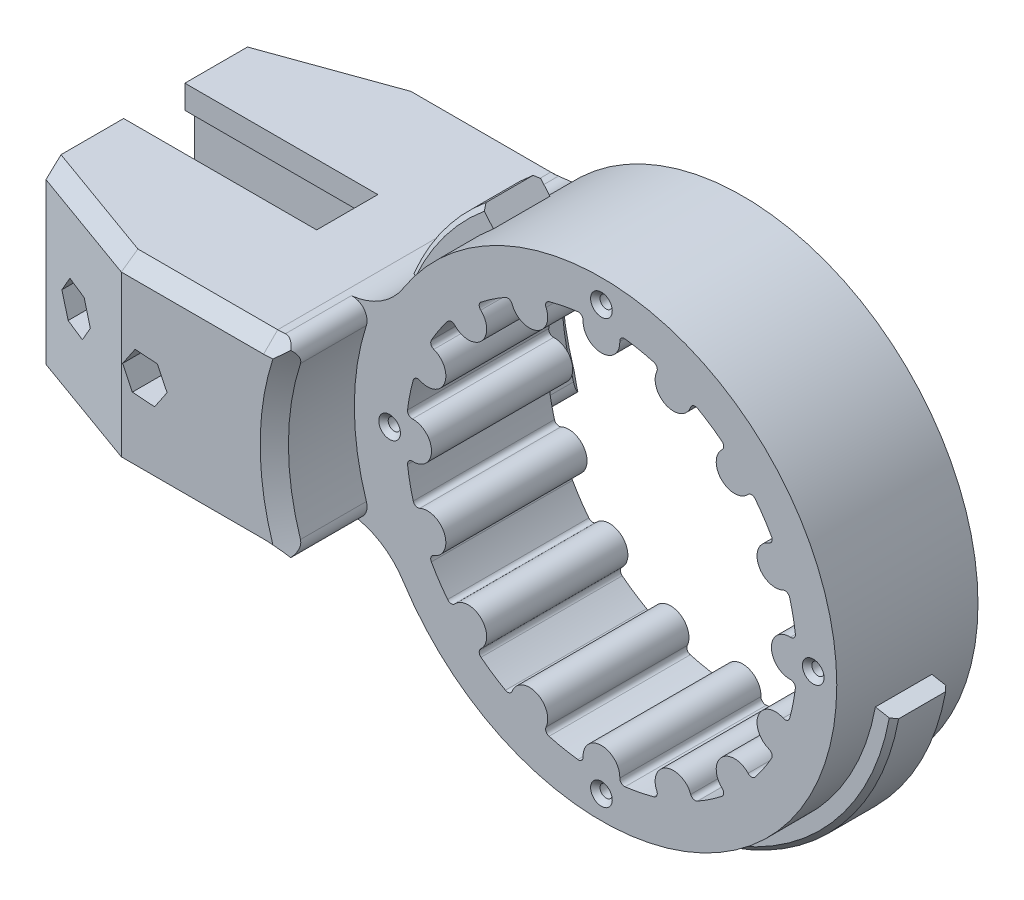
SolidWorks part; units mm, degrees
ref_plane "Front Plane" through (0, 0, 0) normal (0, 0, 1) x (1, 0, 0)
ref_plane "Top Plane" through (0, 0, 0) normal (0, 1, 0) x (1, 0, 0)
ref_plane "Right Plane" through (0, 0, 0) normal (1, 0, 0) x (0, 0, -1)
sketch "Sketch1" plane through (0, 0, 0) normal (0, 0, 1) x (1, 0, 0)
  circle A0 centre (0, 0) radius 50
  dimension "D1" = 100
extrude "Boss-Extrude1" add sketch "Sketch1" along normal blind 30
sketch "Sketch4" plane through (0, 0, 0) normal (0, 0, -1) x (-1, 0, 0)
  line L0 (50, 0) -> (110, 0) construction
  line L1 (45.8258, -20) -> (110, -20)
  line L2 (45.8258, 20) -> (110, 20)
  line L3 (110, 20) -> (110, -20)
  line L4 (0, 20) -> (110, 20) construction
  line L5 (0, 0) -> (110, 0) construction
  line L6 (0, -20) -> (110, -20) construction
  circle A0 centre (0, 0) radius 50 construction
  arc A1 (45.8258, -20) -> (45.8258, 20) centre (0, 0) ccw
  dimension "D3" = 110
  dimension "D1" = 20
  dimension "D2" = 20
extrude "Boss-Extrude2" add sketch "Sketch4" against normal up to surface (30 mm away) up to face at (50, 0, 30)
sketch "Sketch5" plane through (0, 0, 0) normal (0, 0, -1) x (-1, 0, 0)
  line L2 (110, -20) -> (110, 20)
  line L3 (110, 20) -> (48.5412, 20)
  line L5 (48.5412, -20) -> (110, -20)
  line L6 (0, 0) -> (139.0391, 0) construction
  arc A0 (48.5412, -20) -> (48.5412, 20) centre (0, 0) ccw
  dimension "D1" = 105
  dimension "D2" = 40
  dimension "D3" = 110
extrude "Boss-Extrude3" add sketch "Sketch5" along normal blind 17
sketch "Sketch6" plane through (0, 0, 30) normal (0, 0, 1) x (1, 0, 0)
  line L0 (-110, 0) -> (0, 0) construction
  line L6 (-110, -20) -> (-48.5412, -20)
  line L7 (-110, 20) -> (-110, -20)
  line L8 (-48.5412, 20) -> (-110, 20)
  arc A2 (-48.5412, 20) -> (-48.5412, -20) centre (0, 0) ccw
  dimension "D1" = 52.5
  dimension "D2" = 40
  dimension "D3" = 110
extrude "Boss-Extrude4" add sketch "Sketch6" along normal blind 17
sketch "Sketch7" plane through (0, 20, 0) normal (0, 1, 0) x (1, 0, 0)
  line L0 (50, -15) -> (-110, -15) construction
  line L1 (50, -30) -> (50, 0) construction
  line L2 (-110, -47) -> (-110, 17) construction
  line L4 (-151, -8.5) -> (-69, -8.5)
  line L5 (-151, -8.5) -> (-151, -21.5)
  line L6 (-151, -21.5) -> (-69, -21.5)
  line L7 (-69, -8.5) -> (-69, -21.5)
  line L8 (-151, -8.5) -> (-69, -21.5) construction
  line L9 (-151, -21.5) -> (-69, -8.5) construction
  dimension "D1" = 13
  dimension "D2" = 41
extrude "Cut-Extrude3" cut sketch "Sketch7" against normal through all
sketch "Sketch8" plane through (0, 20, 0) normal (0, 1, 0) x (1, 0, 0)
  line L0 (-110, 8) -> (-85, 17)
  line L1 (-110, -8.5) -> (-110, 17) construction
  line L2 (-110, 17) -> (-48.5412, 17) construction
  line L3 (-69, -15) -> (-102.4865, -15) construction
  line L4 (-69, -21.5) -> (-69, -8.5) construction
  line L5 (-110, -38) -> (-85, -47)
  line L6 (-110, -47) -> (-110, -21.5) construction
  line L7 (-48.5412, -47) -> (-110, -47) construction
  line L8 (-110, 17) -> (-85, 17)
  line L9 (-110, 8) -> (-110, 17)
  line L10 (-110, -47) -> (-110, -38)
  line L11 (-85, -47) -> (-110, -47)
  dimension "D1" = 9
  dimension "D2" = 25
extrude "Cut-Extrude4" cut sketch "Sketch8" against normal through all
fillet "Fillet3" radius 15 2 edges at (-45.8258, 20, 15) (-45.8258, -20, 15)
sketch "Sketch10" plane through (-110, 0, 0) normal (-1, 0, 0) x (0, 0, 1)
  line L0 (15, 20) -> (15, -20) construction
  line L1 (47, 20) -> (-17, 20) construction
  line L2 (-17, -20) -> (47, -20) construction
  line L3 (21.5, -20) -> (21.5, 20) construction
  line L4 (6.5, 15) -> (23.5, 15)
  line L5 (6.5, 15) -> (6.5, -15)
  line L6 (6.5, -15) -> (23.5, -15)
  line L7 (23.5, 15) -> (23.5, -15)
  line L8 (6.5, 15) -> (23.5, -15) construction
  line L9 (6.5, -15) -> (23.5, 15) construction
  point P6 (15, 0)
  dimension "D1" = 30
  dimension "D2" = 2
extrude "Cut-Extrude5" cut sketch "Sketch10" against normal blind 41
sketch "Sketch11" plane through (0, 0, -17) normal (0, 0, -1) x (-1, 0, 0)
  line L0 (110, 0) -> (45.4033, 0) construction
  line L1 (110, -20) -> (110, 20) construction
  circle A0 centre (100, 0) radius 2.75
  circle A1 centre (80, 0) radius 2.75
  dimension "D3" = 5.5
  dimension "D1" = 10
  dimension "D2" = 20
extrude "Cut-Extrude6" cut sketch "Sketch11" against normal through all
sketch "Sketch12" plane through (0, 0, -17) normal (0, 0, -1) x (-1, 0, 0)
  circle A0 centre (80, 0) radius 4.6
  circle A1 centre (100, 0) radius 4.6
  dimension "D1" = 9.2
extrude "Cut-Extrude7" cut sketch "Sketch12" against normal blind 12
sketch "Sketch13" plane through (0, 0, 47) normal (0, 0, 1) x (1, 0, 0)
  line L1 (-104.7224, 0.3346) -> (-102.651, -3.9225)
  line L2 (-102.651, -3.9225) -> (-97.9285, -4.257)
  line L3 (-97.9285, -4.257) -> (-95.2776, -0.3346)
  line L4 (-95.2776, -0.3346) -> (-97.349, 3.9225)
  line L5 (-97.349, 3.9225) -> (-102.0715, 4.257)
  line L6 (-102.0715, 4.257) -> (-104.7224, 0.3346)
  line L7 (-84.7224, 0.3346) -> (-82.651, -3.9225)
  line L8 (-82.651, -3.9225) -> (-77.9285, -4.257)
  line L9 (-77.9285, -4.257) -> (-75.2776, -0.3346)
  line L10 (-75.2776, -0.3346) -> (-77.349, 3.9225)
  line L11 (-77.349, 3.9225) -> (-82.0715, 4.257)
  line L12 (-82.0715, 4.257) -> (-84.7224, 0.3346)
  circle A0 centre (-100, 0) radius 4.1 construction
  circle A1 centre (-80, 0) radius 4.1 construction
  dimension "D1" = 8.2
extrude "Cut-Extrude8" cut sketch "Sketch13" against normal blind 12
sketch3d "3DSketch1"
  line L0 (-54.7723, 20, 47) -> (-85, 20, 47) construction
  line L1 (-85, -20, 47) -> (-85, 20, 47) construction
  point P0 (-54.8705, 20, 47)
  point P1 (-85, 11.3679, 47)
  point P4 (-110, 20, 38)
chamfer "Chamfer1" distance 3 angle 45 7 edges at (-97.5, 20, 42.5) (-69.8861, 20, 47) (-52.5, 0, 47) (-97.5, -20, 42.5) (-69.8861, -20, 47) (-51.1795, -20.4366, 47) (-51.1795, 20.4366, 47)
chamfer "Chamfer2" distance 3 angle 45 7 edges at (-97.5, -20, -12.5) (-69.8861, -20, -17) (-52.5, 0, -17) (-69.8861, 20, -17) (-97.5, 20, -12.5) (-51.1795, 20.4366, -17) (-51.1795, -20.4366, -17)
ref_plane "Plane2" through (0, 0, 15) normal (0, 0, 1) x (1, 0, 0)
fillet "Fillet5" radius 3 4 edges at (-47.7959, -21.7211, -7) (-47.7959, -21.7211, 37) (-47.7959, 21.7211, -7) (-47.7959, 21.7211, 37)
sketch "Sketch17" plane through (0, 0, 30) normal (0, 0, 1) x (1, 0, 0)
  circle A0 centre (0, 0) radius 45 construction
  circle A1 centre (-45, 0) radius 1.3
  circle A2 centre (0, 45) radius 1.3
  circle A3 centre (45, 0) radius 1.3
  circle A4 centre (0, -45) radius 1.3
  point P14 (0, 0)
  point P15 (0, 0)
  dimension "D1" = 90
  dimension "D2" = 2.6
  dimension "D3" = 4
extrude "Cut-Extrude10" cut sketch "Sketch17" against normal blind 93
chamfer "Chamfer3" distance 1 angle 45 4 edges at (-43.7, 0, 30) (1.3, 45, 30) (46.3, 0, 30) (1.3, -45, 30)
sketch "Sketch25" plane through (0, 0, 15) normal (0, 0, 1) x (1, 0, 0)
  circle A0 centre (0, 0) radius 54
  circle A1 centre (0, 0) radius 50
  arc A2 (-42.1325, -26.9231) -> (-42.1325, 26.9231) centre (0, 0) ccw construction
  dimension "D1" = 4
extrude "Boss-Extrude8" add sketch "Sketch25" along normal mid plane 12
sketch "Sketch26" plane through (0, 0, 21) normal (0, 0, 1) x (1, 0, 0)
  line L0 (53.1342, -9.6311) -> (49.1983, -8.9177)
  line L2 (-34.5124, 41.5319) -> (-31.9559, 38.4554)
  arc A0 (-49.8155, -20.8426) -> (-49.8155, 20.8426) centre (0, 0) ccw construction
  arc A1 (-42.1325, -26.9231) -> (-42.1325, 26.9231) centre (0, 0) ccw construction
  arc A2 (53.1342, -9.6311) -> (-34.5124, 41.5319) centre (0, 0) ccw
  arc A3 (49.1983, -8.9177) -> (-31.9559, 38.4554) centre (0, 0) ccw
  dimension "D1" = 140
extrude "Cut-Extrude12" cut sketch "Sketch26" against normal blind 15
chamfer "Chamfer4" distance 1 angle 45 4 edges at (5.8462, -53.6826, 21) (5.8462, -53.6826, 9) (-43.4144, 32.1122, 9) (-43.4144, 32.1122, 21)
sketch "Sketch27" plane through (0, 0, 30) normal (0, 0, 1) x (1, 0, 0)
  circle A0 centre (0, 0) radius 40 construction
  arc A1 (-41.338, -3.6633) -> (-41.338, 3.6633) centre (-40, 0) ccw
  arc A2 (-39.5932, 12.4349) -> (-36.7894, 19.2038) centre (-36.9552, 15.3073) ccw
  arc A3 (-31.8207, 26.64) -> (-26.64, 31.8207) centre (-28.2843, 28.2843) ccw
  arc A4 (-19.2038, 36.7894) -> (-12.4349, 39.5932) centre (-15.3073, 36.9552) ccw
  arc A5 (-3.6633, 41.338) -> (3.6633, 41.338) centre (0, 40) ccw
  arc A6 (12.4349, 39.5932) -> (19.2038, 36.7894) centre (15.3073, 36.9552) ccw
  arc A7 (26.64, 31.8207) -> (31.8207, 26.64) centre (28.2843, 28.2843) ccw
  arc A8 (36.7894, 19.2038) -> (39.5932, 12.4349) centre (36.9552, 15.3073) ccw
  arc A9 (41.338, 3.6633) -> (41.338, -3.6633) centre (40, 0) ccw
  arc A10 (39.5932, -12.4349) -> (36.7894, -19.2038) centre (36.9552, -15.3073) ccw
  arc A11 (31.8207, -26.64) -> (26.64, -31.8207) centre (28.2843, -28.2843) ccw
  arc A12 (19.2038, -36.7894) -> (12.4349, -39.5932) centre (15.3073, -36.9552) ccw
  arc A13 (3.6633, -41.338) -> (-3.6633, -41.338) centre (0, -40) ccw
  arc A14 (-12.4349, -39.5932) -> (-19.2038, -36.7894) centre (-15.3073, -36.9552) ccw
  arc A15 (-26.64, -31.8207) -> (-31.8207, -26.64) centre (-28.2843, -28.2843) ccw
  arc A16 (-36.7894, -19.2038) -> (-39.5932, -12.4349) centre (-36.9552, -15.3073) ccw
  arc A17 (-12.4349, -39.5932) -> (-3.6633, -41.338) centre (0, 0) ccw
  arc A18 (3.6633, -41.338) -> (12.4349, -39.5932) centre (0, 0) ccw
  arc A19 (19.2038, -36.7894) -> (26.64, -31.8207) centre (0, 0) ccw
  arc A20 (31.8207, -26.64) -> (36.7894, -19.2038) centre (0, 0) ccw
  arc A21 (39.5932, -12.4349) -> (41.338, -3.6633) centre (0, 0) ccw
  arc A22 (41.338, 3.6633) -> (39.5932, 12.4349) centre (0, 0) ccw
  arc A23 (36.7894, 19.2038) -> (31.8207, 26.64) centre (0, 0) ccw
  arc A24 (26.64, 31.8207) -> (19.2038, 36.7894) centre (0, 0) ccw
  arc A25 (12.4349, 39.5932) -> (3.6633, 41.338) centre (0, 0) ccw
  arc A26 (-3.6633, 41.338) -> (-12.4349, 39.5932) centre (0, 0) ccw
  arc A27 (-19.2038, 36.7894) -> (-26.64, 31.8207) centre (0, 0) ccw
  arc A28 (-31.8207, 26.64) -> (-36.7894, 19.2038) centre (0, 0) ccw
  arc A29 (-39.5932, 12.4349) -> (-41.338, 3.6633) centre (0, 0) ccw
  arc A30 (-41.338, -3.6633) -> (-39.5932, -12.4349) centre (0, 0) ccw
  arc A31 (-36.7894, -19.2038) -> (-31.8207, -26.64) centre (0, 0) ccw
  arc A32 (-26.64, -31.8207) -> (-19.2038, -36.7894) centre (0, 0) ccw
  point P38 (0, 0)
  dimension "D1" = 80
  dimension "D2" = 7.8
  dimension "D4" = 1.5
  dimension "D3" = 16
extrude "Cut-Extrude13" cut sketch "Sketch27" against normal through all
fillet "Fillet6" radius 1 32 edges at (19.2038, -36.7894, 15) (26.64, -31.8207, 15) (31.8207, -26.64, 15) (36.7894, -19.2038, 15) (39.5932, -12.4349, 15) (41.338, -3.6633, 15) (41.338, 3.6633, 15) (39.5932, 12.4349, 15) (31.8207, 26.64, 15) (19.2038, 36.7894, 15) (3.6633, 41.338, 15) (-12.4349, 39.5932, 15) (36.7894, 19.2038, 15) (26.64, 31.8207, 15) (12.4349, 39.5932, 15) (-3.6633, 41.338, 15) (-19.2038, 36.7894, 15) (-31.8207, 26.64, 15) (-26.64, 31.8207, 15) (-36.7894, 19.2038, 15) (-39.5932, 12.4349, 15) (-41.338, 3.6633, 15) (-41.338, -3.6633, 15) (-36.7894, -19.2038, 15) (-39.5932, -12.4349, 15) (-31.8207, -26.64, 15) (-26.64, -31.8207, 15) (3.6633, -41.338, 15) (12.4349, -39.5932, 15) (-12.4349, -39.5932, 15) (-19.2038, -36.7894, 15) (-3.6633, -41.338, 15)
